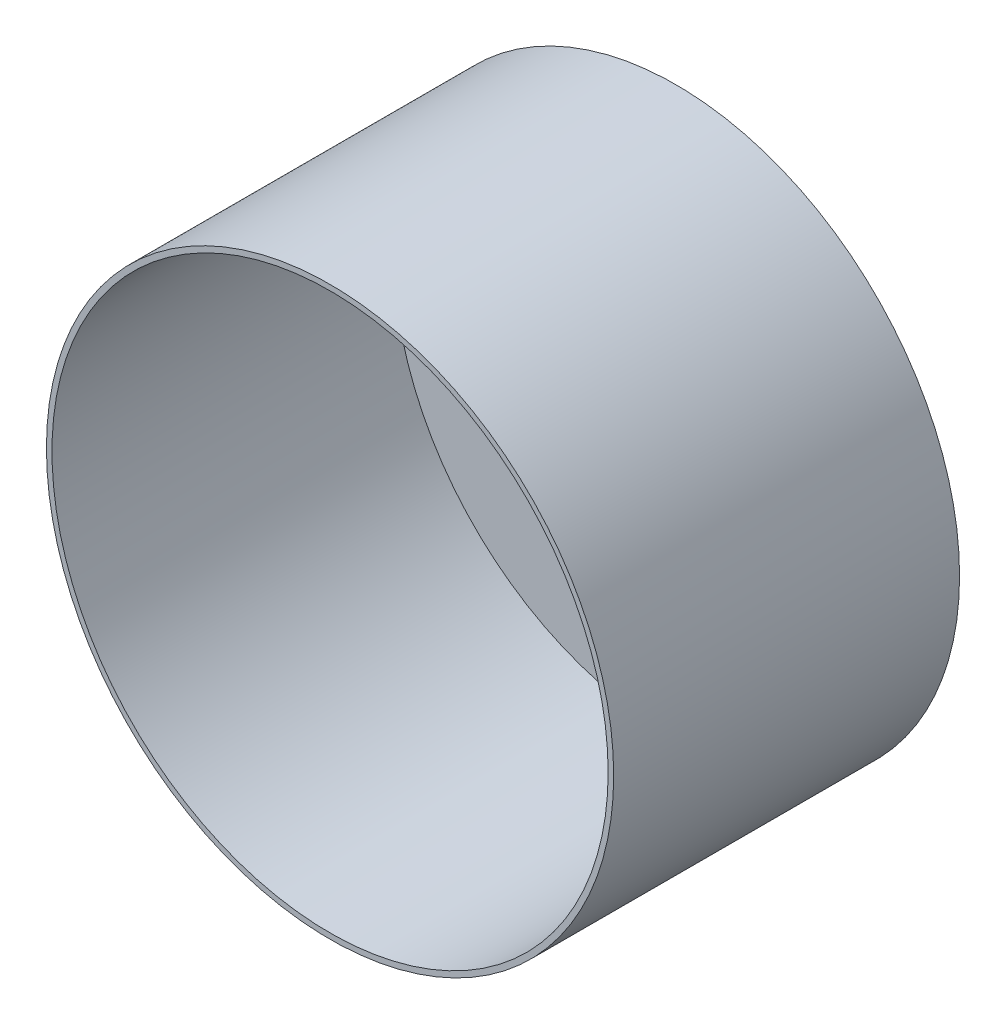
SolidWorks part; units mm, degrees
ref_plane "前视基准面" through (0, 0, 0) normal (0, 0, 1) x (1, 0, 0)
ref_plane "上视基准面" through (0, 0, 0) normal (0, 1, 0) x (1, 0, 0)
ref_plane "右视基准面" through (0, 0, 0) normal (1, 0, 0) x (0, 0, -1)
other "Configuration Table"
sketch "Sketch1" plane through (0, 0, 0) normal (0, 0, 1) x (1, 0, 0)
  circle A0 centre (0, 0) radius 50.5
  circle A1 centre (0, 0) radius 100.5
  circle A2 centre (0, 0) radius 102.5
extrude "Boss-Extrude1" add sketch "Sketch1" along normal blind 1.5 contours A1 A0 region at (-97.6574, 0, 0)
extrude "Boss-Extrude2" add sketch "Sketch1<3>" along normal blind 125 contours A2 A1 region at (-102.2101, 0, 0)
sketch "Sketch1<3>" plane through (0, 0, 0) normal (0, 0, 1) x (1, 0, 0) same geometry as "Sketch1"
